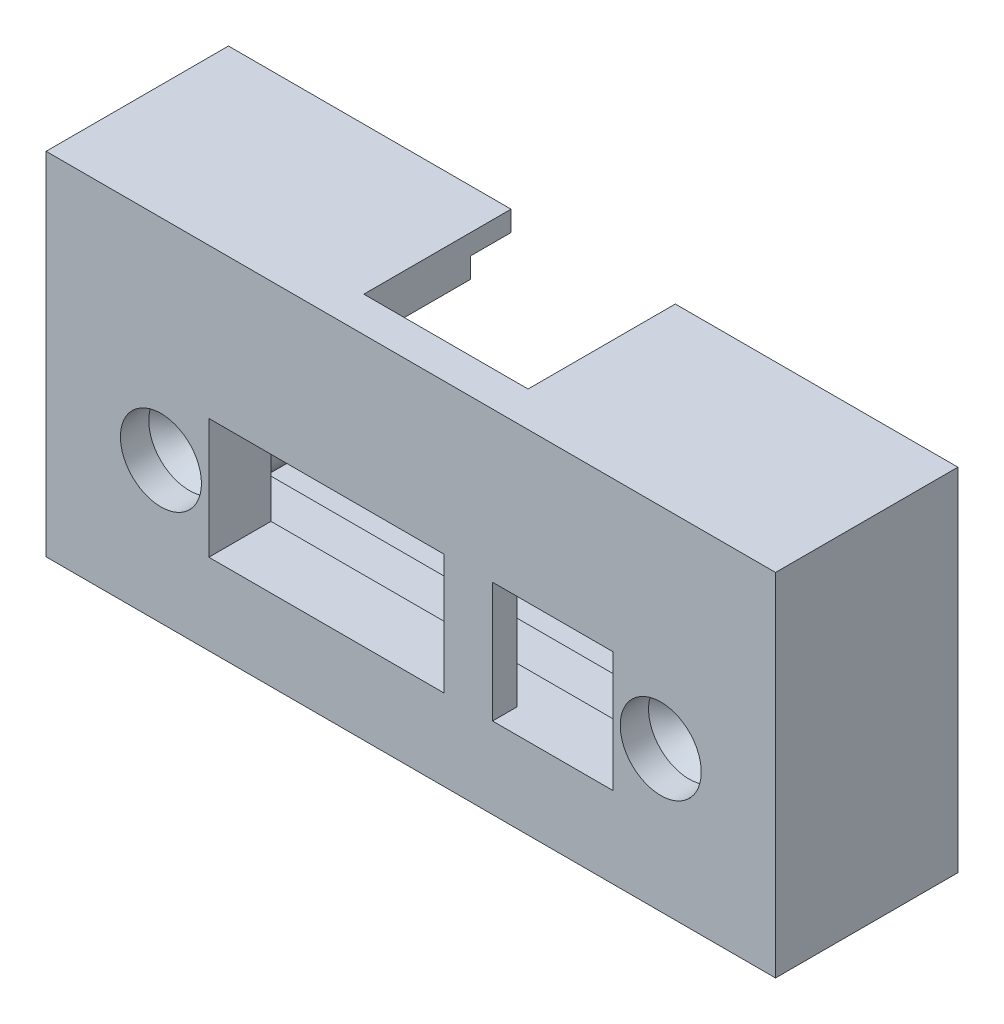
SolidWorks part; units mm, degrees
ref_plane "Front Plane" through (0, 0, 0) normal (0, 0, 1) x (1, 0, 0)
ref_plane "Top Plane" through (0, 0, 0) normal (0, 1, 0) x (1, 0, 0)
ref_plane "Right Plane" through (0, 0, 0) normal (1, 0, 0) x (0, 0, -1)
sketch "Sketch1" plane through (0, 0, 0) normal (0, 0, 1) x (1, 0, 0)
  line L4 (0, -1009.95) -> (0, 48990.05) construction
  line L6 (-27, -15.95) -> (27, -15.95)
  line L7 (-27, -15.95) -> (-27, 10.05)
  line L8 (-14.95, -1.05) -> (-14.95, -9.95)
  line L9 (-14.95, -9.95) -> (14.95, -9.95)
  line L10 (14.95, -9.95) -> (14.95, -1.05)
  line L11 (14.95, -1.05) -> (-14.95, -1.05)
  line L12 (-14.95, -1.05) -> (-14.95, -9.95)
  line L13 (-14.95, -9.95) -> (14.95, -9.95)
  line L14 (14.95, -9.95) -> (14.95, -1.05)
  line L15 (14.95, -1.05) -> (-14.95, -1.05)
  line L16 (-27, 10.05) -> (27, 10.05)
  line L17 (27, -15.95) -> (27, 10.05)
  line L18 (-27, -15.95) -> (27, 10.05) construction
  line L19 (-27, 10.05) -> (27, -15.95) construction
  point P1 (0, -2.95)
  point P3 (0, -9.95)
  dimension "D2" = 26
  dimension "D3" = 54
  dimension "D4" = 6
  dimension "D1" = 0.2
extrude "Boss-Extrude1" add sketch "Sketch1" along normal up to surface (4.6 mm away)
sketch "Sketch2" plane through (0, 0, 4.6) normal (0, 0, 1) x (1, 0, 0)
  line L0 (-14.95, -1.05) -> (14.95, -1.05) construction
  line L1 (6.05, -1.05) -> (2.45, -1.05)
  line L2 (6.05, -1.05) -> (6.05, -9.95)
  line L3 (6.05, -9.95) -> (2.45, -9.95)
  line L4 (2.45, -1.05) -> (2.45, -9.95)
  line L5 (14.95, -9.95) -> (-14.95, -9.95) construction
  line L6 (2.25, -8.75) -> (2.25, -2.25) construction
  line L7 (6.25, -2.25) -> (6.25, -8.75) construction
  dimension "D1" = 0.2
  dimension "D2" = 0.2
extrude "Boss-Extrude2" add sketch "Sketch2" against normal offset from surface (1.8 mm away) 0.2
sketch "Sketch3" plane through (0, 0, 0) normal (0, 0, -1) x (-1, 0, 0)
  circle A0 centre (-18.5, -5.5) radius 3.45
  circle A1 centre (18.5, -5.5) radius 3.45
  arc A2 (18.5, -9.25) -> (18.5, -1.75) centre (18.5, -5.5) ccw construction
  arc A3 (-18.5, -1.75) -> (-18.5, -9.25) centre (-18.5, -5.5) ccw construction
  dimension "D1" = 0.3
  dimension "D2" = 0.3
extrude "Boss-Extrude3" add sketch "Sketch3" along normal up to surface (7.4 mm away)
sketch "Sketch4" plane through (0, 0, 0) normal (0, 0, -1) x (-1, 0, 0)
  line L4 (-24, 7.05) -> (-24, -12.95)
  line L5 (-24, -12.95) -> (24, -12.95)
  line L6 (24, -12.95) -> (24, 7.05)
  line L7 (24, 7.05) -> (-24, 7.05)
  line L8 (-27, 10.05) -> (-27, -15.95)
  line L9 (-27, -15.95) -> (27, -15.95)
  line L10 (27, -15.95) -> (27, 10.05)
  line L11 (27, 10.05) -> (-27, 10.05)
  line L12 (-27, 10.05) -> (-27, -15.95)
  line L13 (-27, -15.95) -> (27, -15.95)
  line L14 (27, -15.95) -> (27, 10.05)
  line L15 (27, 10.05) -> (-27, 10.05)
  dimension "D1" = 0
  dimension "D2" = 3
extrude "Boss-Extrude4" add sketch "Sketch4" along normal up to surface (8.9 mm away)
sketch "Sketch5" plane through (0, 0, -8.9) normal (0, 0, -1) x (-1, 0, 0)
  line L4 (25.5, 8.55) -> (-25.5, 8.55)
  line L5 (-25.5, 8.55) -> (-25.5, -14.45)
  line L6 (-25.5, -14.45) -> (25.5, -14.45)
  line L7 (25.5, -14.45) -> (25.5, 8.55)
  line L8 (24, 7.05) -> (-24, 7.05)
  line L9 (-24, 7.05) -> (-24, -12.95)
  line L10 (-24, -12.95) -> (24, -12.95)
  line L11 (24, -12.95) -> (24, 7.05)
  line L12 (24, 7.05) -> (-24, 7.05)
  line L13 (-24, 7.05) -> (-24, -12.95)
  line L14 (-24, -12.95) -> (24, -12.95)
  line L15 (24, -12.95) -> (24, 7.05)
  dimension "D1" = 0
  dimension "D2" = 1.5
extrude "Cut-Extrude1" cut sketch "Sketch5" against normal blind 3
sketch "Sketch6" plane through (0, 0, -7.4) normal (0, 0, -1) x (-1, 0, 0)
  circle A0 centre (-18.5, -5.5) radius 1.6
  circle A1 centre (18.5, -5.5) radius 1.6
  circle A2 centre (-18.5, -5.5) radius 1.6 construction
  dimension "D1" = 0
extrude "Cut-Extrude2" cut sketch "Sketch6" against normal up to surface (12 mm away)
sketch "Sketch7" plane through (0, 10.05, 0) normal (0, 1, 0) x (1, 0, 0)
  line L0 (5.08, 1.8) -> (5.08, 5.9) construction
  line L1 (6.08, -2) -> (-6.08, -2)
  line L2 (6.08, -2) -> (6.08, 8.9)
  line L3 (6.08, 8.9) -> (-6.08, 8.9)
  line L4 (-6.08, -2) -> (-6.08, 8.9)
  line L5 (-5.08, 5.9) -> (-5.08, 1.8) construction
  line L6 (-24, 0) -> (24, 0) construction
  line L8 (27, 8.9) -> (-27, 8.9) construction
  dimension "D1" = 1
  dimension "D2" = 1
  dimension "D3" = 2
extrude "Cut-Extrude3" cut sketch "Sketch7" against normal up to surface (3 mm away) up to face at (0, 7.05, -2.95)
ref_plane "Plane1" through (0, 0, 2.6) normal (0, 0, 1) x (1, 0, 0)
sketch "Sketch8" plane through (0, 0, 2.6) normal (0, 0, 1) x (1, 0, 0)
  circle A0 centre (-18.5, -5.5) radius 3
  circle A1 centre (18.5, -5.5) radius 3
  dimension "D1" = 6
extrude "Cut-Extrude4" cut sketch "Sketch8" along normal through all
chamfer "Chamfer1" distance 1.5 angle 45 2 edges at (-16.9, -5.5, 2.6) (20.1, -5.5, 2.6)
